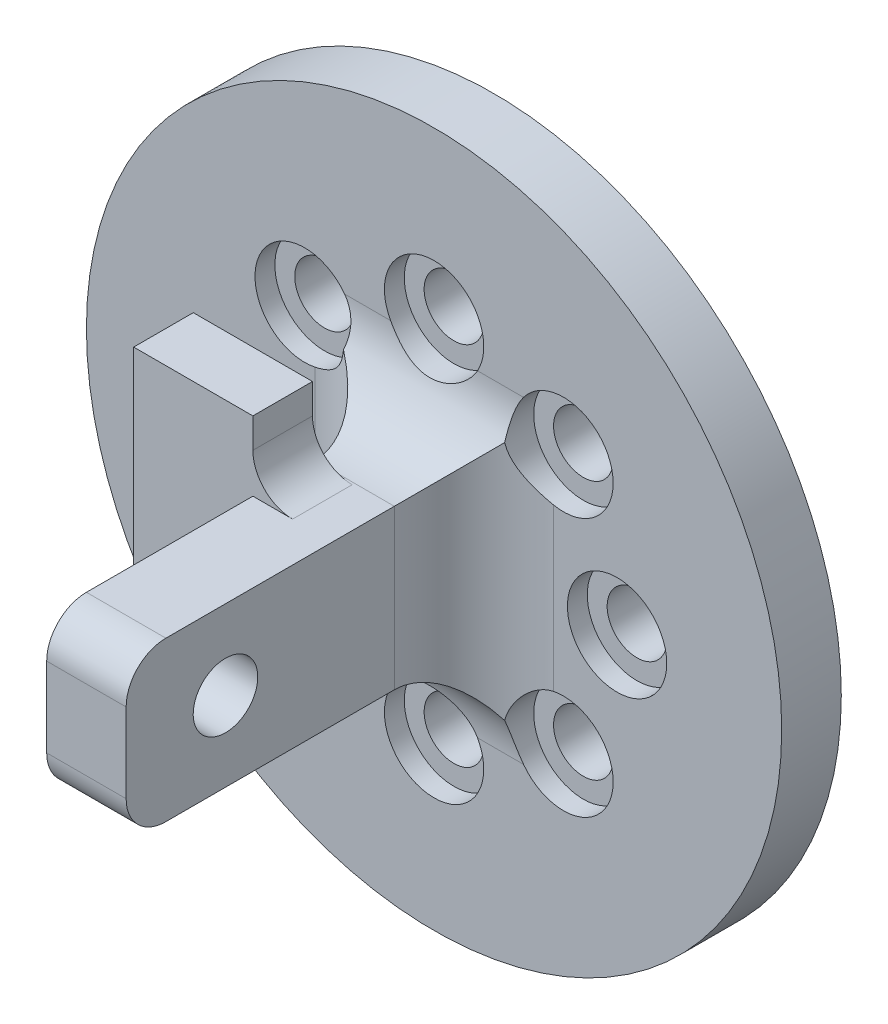
SolidWorks part; units mm, degrees
ref_plane "Front Plane" through (0, 0, 0) normal (0, 0, 1) x (1, 0, 0)
ref_plane "Top Plane" through (0, 0, 0) normal (0, 1, 0) x (1, 0, 0)
ref_plane "Right Plane" through (0, 0, 0) normal (1, 0, 0) x (0, 0, -1)
sketch "Sketch1" plane through (0, 0, 0) normal (0, 0, 1) x (1, 0, 0)
  circle A0 centre (0, 0) radius 35
  circle A1 centre (0, 18.4254) radius 3
  circle A2 centre (13.0287, 13.0287) radius 3
  circle A3 centre (18.4254, 0) radius 3
  circle A4 centre (13.0287, -13.0287) radius 3
  circle A5 centre (0, -18.4254) radius 3
  circle A6 centre (-13.0287, -13.0287) radius 3
  circle A7 centre (-18.4254, 0) radius 3
  circle A8 centre (-13.0287, 13.0287) radius 3
  dimension "D1" = 70
  dimension "D2" = 8
extrude "Boss-Extrude1" add sketch "Sketch1" along normal blind 6
sketch "Sketch4" plane through (0, 0, 6) normal (0, 0, 1) x (1, 0, 0)
  circle A0 centre (0, 18.4254) radius 5
  circle A1 centre (13.0287, 13.0287) radius 5
  circle A2 centre (18.4254, 0) radius 5
  circle A3 centre (13.0287, -13.0287) radius 5
  circle A4 centre (0, -18.4254) radius 5
  circle A5 centre (-13.0287, -13.0287) radius 5
  circle A6 centre (-18.4254, 0) radius 5
  circle A7 centre (-13.0287, 13.0287) radius 5
  dimension "D1" = 8
extrude "Cut-Extrude1" cut sketch "Sketch4" against normal blind 2
sketch "Sketch5" plane through (0, 0, 6) normal (0, 0, 1) x (1, 0, 0)
  line L1 (-4, 8) -> (4, 8)
  line L2 (-4, 8) -> (-4, -8)
  line L3 (-4, -8) -> (4, -8)
  line L4 (4, 8) -> (4, -8)
  line L5 (-4, 8) -> (4, -8) construction
  line L6 (-4, -8) -> (4, 8) construction
  point P0 (0, 0)
  dimension "D1" = 16
  dimension "D2" = 8
extrude "Boss-Extrude2" add sketch "Sketch5" along normal blind 35
sketch "Sketch6" plane through (4, 0, 0) normal (1, 0, 0) x (0, 0, -1)
  line L0 (-41, -8) -> (-41, 8) construction
  circle A0 centre (-31, 0) radius 3.25
  dimension "D1" = 6.5
  dimension "D2" = 10
extrude "Cut-Extrude2" cut sketch "Sketch6" against normal through all
fillet "Fillet1" radius 8 4 edges at (0, -8, 6) (4, 0, 6) (0, 8, 6) (-4, 0, 6)
fillet "Fillet2" radius 4 2 edges at (0, 8, 41) (0, -8, 41)
sketch "Sketch7" plane through (-4, 0, 0) normal (-1, 0, 0) x (0, 0, 1)
  line L1 (20.24, 15) -> (14.24, 15)
  line L2 (20.24, 15) -> (20.24, -15)
  line L3 (20.24, -15) -> (14.24, -15)
  line L4 (14.24, 15) -> (14.24, -15)
  line L5 (20.24, 15) -> (14.24, -15) construction
  line L6 (20.24, -15) -> (14.24, 15) construction
  circle A1 centre (31, 0) radius 3.25 construction
  point P0 (17.24, 0)
  dimension "D1" = 10.76
  dimension "D2" = 30
  dimension "D3" = 6
extrude "Boss-Extrude3" add sketch "Sketch7" along normal blind 12
fillet "Fillet3" radius 4 2 edges at (-4, -8, 17.24) (-4, 8, 17.24)
